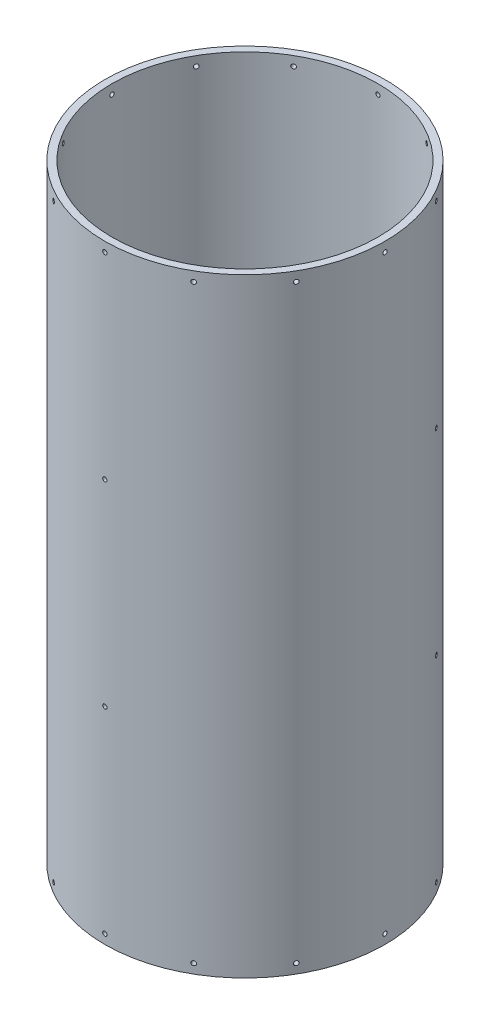
SolidWorks part; units mm, degrees
material "PVC Rigid"
ref_plane "Front Plane" through (0, 0, 0) normal (0, 0, 1) x (1, 0, 0)
ref_plane "Top Plane" through (0, 0, 0) normal (0, 1, 0) x (1, 0, 0)
ref_plane "Right Plane" through (0, 0, 0) normal (1, 0, 0) x (0, 0, -1)
sketch "Sketch1" plane through (0, 0, 0) normal (0, 1, 0) x (1, 0, 0)
  circle A0 centre (0, 0) radius 93.6625
  circle A1 centre (0, 0) radius 88.9
  dimension "D1" = 187.325
  dimension "D2" = 177.8
extrude "Boss-Extrude1" add sketch "Sketch1" along normal mid plane 407.162
ref_plane "Plane1" through (0, 0, 93.6625) normal (0, 0, 1) x (1, 0, 0)
sketch "Sketch3" plane through (0, 0, 93.6625) normal (0, 0, 1) x (1, 0, 0)
  line L0 (0, -55) -> (0, 55) construction
  line L1 (-93.6625, -203.581) -> (93.6625, -203.581) construction
  circle A0 centre (0, -197.231) radius 1.4351
  dimension "D1" = 2.8702
  dimension "D2" = 6.35
extrude "Cut-Extrude1" cut sketch "Sketch3" against normal blind 19.304
pattern_circular "CirPattern1" count 12 over 360 about axis through (0, 203.581, 0) along (0, -1, 0) of "Cut-Extrude1" reverse direction yes
mirror "Mirror1" about plane through (0, 0, 0) normal (0, 1, 0) of "CirPattern1", "Cut-Extrude1"
sketch "Sketch4" plane through (0, 0, 93.6625) normal (0, 0, 1) x (1, 0, 0)
  line L0 (0, -55) -> (0, 55) construction
  circle A0 centre (0, 65.7606) radius 1.4351
  circle A1 centre (0, -65.7606) radius 1.4351
  circle A2 centre (0, 197.231) radius 1.4351 construction
  circle A3 centre (0, -197.231) radius 1.4351 construction
  dimension "D1" = 131.4704
  dimension "D2" = 131.4704
  dimension "D3" = 2.8702
  dimension "D4" = 2.8702
extrude "Cut-Extrude2" cut sketch "Sketch4" against normal blind 43.18
pattern_circular "CirPattern2" count 3 over 360 about axis through (0, 203.581, 0) along (0, -1, 0) of "Cut-Extrude2" reverse direction yes
